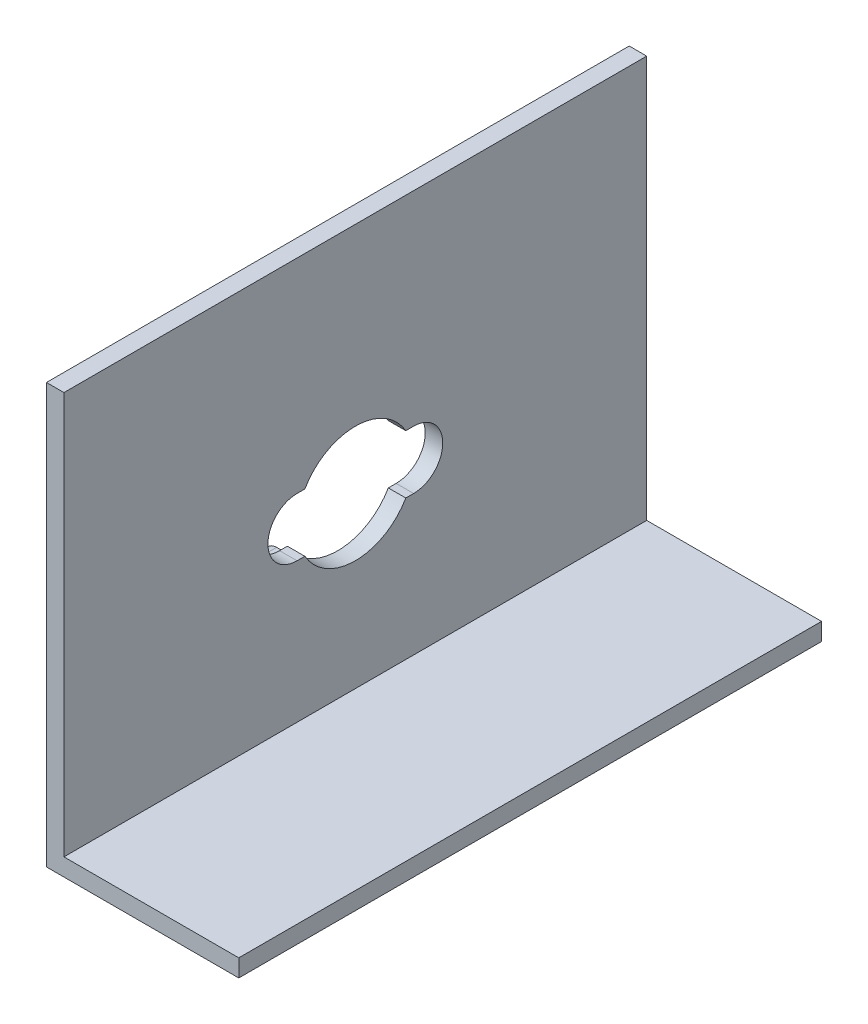
SolidWorks part; units mm, degrees
ref_plane "Front Plane" through (0, 0, 0) normal (0, 0, 1) x (1, 0, 0)
ref_plane "Top Plane" through (0, 0, 0) normal (0, 1, 0) x (1, 0, 0)
ref_plane "Right Plane" through (0, 0, 0) normal (1, 0, 0) x (0, 0, -1)
sketch "Sketch1" plane through (0, 0, 0) normal (0, 0, 1) x (1, 0, 0)
  line L0 (0, 72) -> (3, 72)
  line L1 (3, 3) -> (3, 72)
  line L2 (0, 72) -> (0, 0)
  line L3 (0, 0) -> (33, 0)
  line L4 (33, 0) -> (33, 3)
  line L5 (33, 3) -> (3, 3)
  dimension "D1" = 30
  dimension "D2" = 3
  dimension "D3" = 3
  dimension "D4" = 72
extrude "Boss-Extrude1" add sketch "Sketch1" along normal blind 100
sketch "Sketch2" plane through (0, 0, 0) normal (-1, 0, 0) x (0, 0, 1)
  line L0 (58.6603, 37) -> (60, 37)
  line L1 (40, 32) -> (60, 32) construction
  line L2 (40, 37) -> (41.3397, 37)
  line L3 (40, 27) -> (41.3397, 27)
  line L4 (58.6603, 27) -> (60, 27)
  line L5 (100, 0) -> (0, 0) construction
  line L7 (0, 72) -> (0, 0) construction
  arc A0 (40, 37) -> (40, 27) centre (40, 32) ccw
  arc A1 (60, 27) -> (60, 37) centre (60, 32) ccw
  arc A2 (58.6603, 37) -> (41.3397, 37) centre (50, 32) ccw
  arc A3 (41.3397, 27) -> (58.6603, 27) centre (50, 32) ccw
  point P2 (50, 32)
  dimension "D1" = 5
  dimension "D3" = 20
  dimension "D6" = 5
  dimension "D2" = 20
  dimension "D4" = 5
  dimension "D5" = 5
  dimension "D7" = 10
  dimension "D8" = 10
  dimension "D9" = 1.3397
  dimension "D10" = 1.3397
  dimension "D11" = 32
  dimension "D12" = 50
extrude "Cut-Extrude1" cut sketch "Sketch2" against normal blind 100
ref_plane "Plane1" through (0, 0, 50) normal (0, 0, -1) x (-1, 0, 0)
sketch "Sketch7" plane through (0, 0, 50) normal (0, 0, -1) x (-1, 0, 0)
  line L0 (0, 14.75) -> (15, 14.75)
  line L1 (0, 72) -> (0, 0) construction
  line L2 (15, 14.75) -> (15, 10.75)
  line L3 (15, 10.75) -> (14, 10.75)
  line L4 (14, 10.75) -> (12.75, 12.25)
  line L5 (12.75, 12.25) -> (0, 12.25)
  line L6 (0, 12.25) -> (0, 14.75)
  line L7 (0, 4.5) -> (0, 2)
  line L8 (0, 2) -> (15, 2)
  line L9 (15, 2) -> (15, 6)
  line L10 (15, 6) -> (14, 6)
  line L11 (14, 6) -> (12.75, 4.5)
  line L12 (12.75, 4.5) -> (0, 4.5)
  line L13 (0, 0) -> (-33, 0) construction
  dimension "D1" = 2.5
  dimension "D2" = 2.5
  dimension "D3" = 4
  dimension "D4" = 4
  dimension "D5" = 4.75
  dimension "D6" = 2
  dimension "D7" = 1
  dimension "D8" = 1.25
  dimension "D9" = 1.25
  dimension "D10" = 15
extrude "Boss-Extrude3" add sketch "Sketch7" along normal mid plane 5
fillet "Fillet4" radius 0.5 6 edges at (-12.75, 12.25, 50) (-14, 10.75, 50) (-15, 10.75, 50) (-12.75, 4.5, 50) (-14, 6, 50) (-15, 6, 50)
fillet "Fillet5" radius 2 2 edges at (-15, 14.75, 50) (-15, 2, 50)
